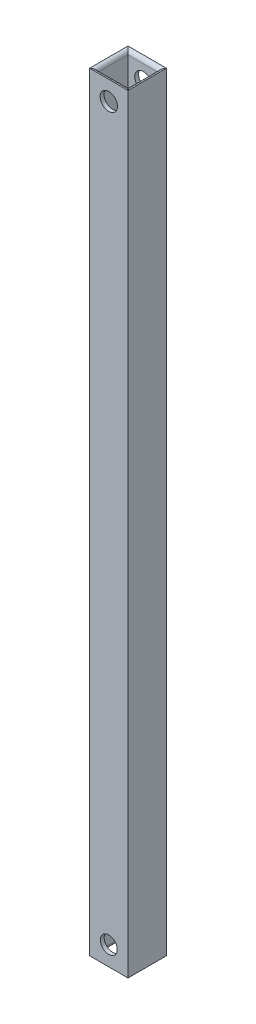
SolidWorks part; units mm, degrees
material "Alumina"
ref_plane "Front Plane" through (0, 0, 0) normal (0, 0, 1) x (1, 0, 0)
ref_plane "Top Plane" through (0, 0, 0) normal (0, 1, 0) x (1, 0, 0)
ref_plane "Right Plane" through (0, 0, 0) normal (1, 0, 0) x (0, 0, -1)
sketch "Sketch1" plane through (0, 0, 0) normal (0, 1, 0) x (1, 0, 0)
  line L1 (-5, 5) -> (5, 5)
  line L2 (-5, 5) -> (-5, -5)
  line L3 (-5, -5) -> (5, -5)
  line L4 (5, 5) -> (5, -5)
  line L5 (-5, 5) -> (5, -5) construction
  line L6 (-5, -5) -> (5, 5) construction
  line L7 (-4, 4) -> (4, 4)
  line L8 (-4, 4) -> (-4, -4)
  line L9 (-4, -4) -> (4, -4)
  line L10 (4, 4) -> (4, -4)
  line L11 (-4, 4) -> (4, -4) construction
  line L12 (-4, -4) -> (4, 4) construction
  point P0 (0, 0)
  point P6 (0, 0)
  dimension "D1" = 10
  dimension "D2" = 10
  dimension "D3" = 8
extrude "Boss-Extrude1" add sketch "Sketch1" along normal blind 200
fillet "Fillet2" radius 1 8 edges at (4, 200, 0) (0, 200, -4) (-4, 200, 0) (0, 200, 4) (-4, 0, 0) (0, 0, 4) (4, 0, 0) (0, 0, -4)
sketch "Sketch2" plane through (0, 0, 5) normal (0, 0, 1) x (1, 0, 0)
  line L0 (5, 200) -> (5, 0) construction
  line L2 (-5, 0) -> (5, 0) construction
  circle A0 centre (0, 5) radius 2.2
  circle A1 centre (0, 195) radius 2.25
  dimension "D1" = 4.4
  dimension "D2" = 4.5
  dimension "D3" = 5
  dimension "D4" = 195
  dimension "D5" = 5
  dimension "D6" = 5
extrude "Cut-Extrude1" cut sketch "Sketch2" against normal through all
